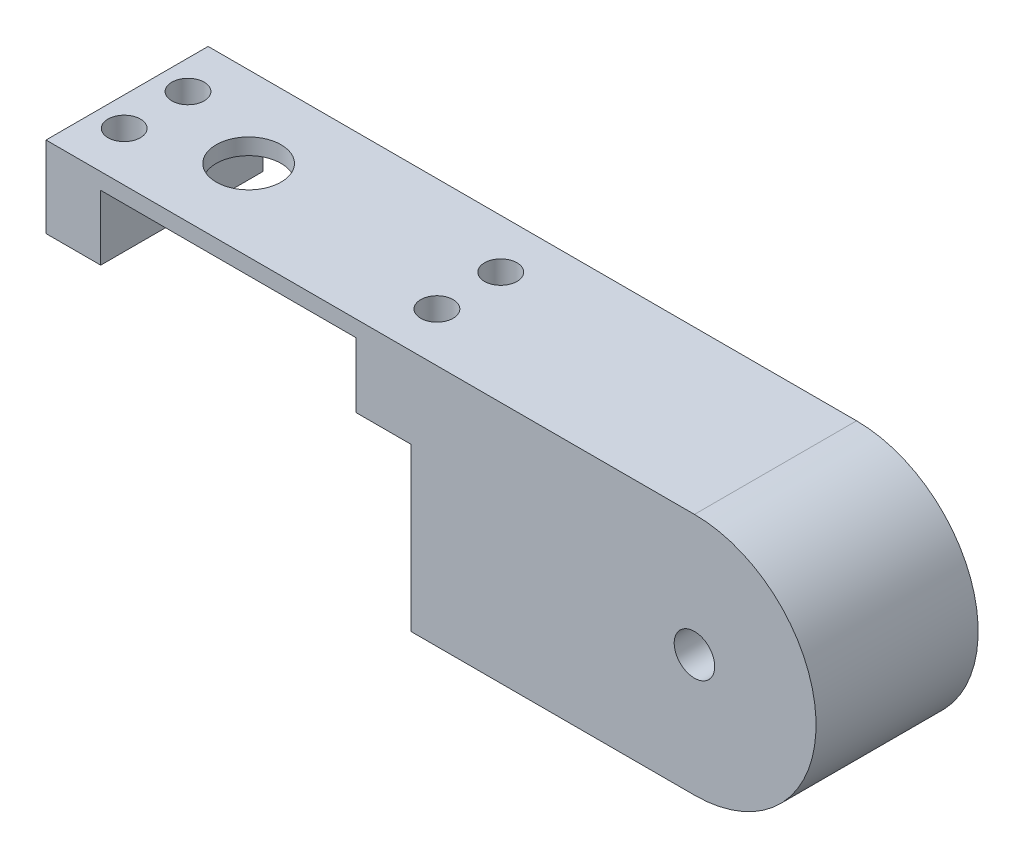
SolidWorks part; units mm, degrees
ref_plane "Front Plane" through (0, 0, 0) normal (0, 0, 1) x (1, 0, 0)
ref_plane "Top Plane" through (0, 0, 0) normal (0, 1, 0) x (1, 0, 0)
ref_plane "Right Plane" through (0, 0, 0) normal (1, 0, 0) x (0, 0, -1)
sketch "Sketch1" plane through (0, 0, 0) normal (0, 0, 1) x (1, 0, 0)
  line L1 (-50.8, -19.05) -> (50.8, -19.05)
  line L2 (-50.8, -19.05) -> (-50.8, 19.05)
  line L3 (-50.8, 19.05) -> (50.8, 19.05)
  line L4 (50.8, -19.05) -> (50.8, 19.05)
  line L5 (-50.8, -19.05) -> (50.8, 19.05) construction
  line L6 (-50.8, 19.05) -> (50.8, -19.05) construction
  circle A1 centre (50.8, 0) radius 19.05
  point P0 (0, 0)
  dimension "D1" = 38.1
  dimension "D2" = 101.6
extrude "Boss-Extrude1" add sketch "Sketch1" along normal blind 25.4 contours L2 L1 L4 L3 | A1
sketch "Sketch11" plane through (0, 0, 25.4) normal (0, 0, 1) x (1, 0, 0)
  circle A0 centre (50.8, 0) radius 3.175
  arc A1 (50.8, -19.05) -> (50.8, 19.05) centre (50.8, 0) ccw construction
  dimension "D1" = 6.35
extrude "Cut-Extrude6" cut sketch "Sketch11" against normal through all
sketch "Sketch12" plane through (0, 0, 25.4) normal (0, 0, 1) x (1, 0, 0)
  line L0 (-50.8, 19.05) -> (50.8, 19.05) construction
  line L1 (-50.8, -19.05) -> (6.35, -19.05)
  line L2 (-50.8, -19.05) -> (-50.8, 16.51)
  line L3 (-50.8, 16.51) -> (6.35, 16.51)
  line L4 (6.35, -19.05) -> (6.35, 16.51)
  dimension "D1" = 2.54
  dimension "D2" = 57.15
extrude "Cut-Extrude7" cut sketch "Sketch12" against normal through all
sketch "Sketch13" plane through (0, 19.05, 0) normal (0, 1, 0) x (1, 0, 0)
  line L5 (-50.8, -25.4) -> (-50.8, 0) construction
  line L6 (-50.8, -12.7) -> (50.8, -12.7) construction
  line L7 (50.8, -25.4) -> (50.8, 0) construction
  circle A1 centre (-31.75, -12.7) radius 5.08
  point P9 (-31.75, -12.7)
  dimension "D2" = 10.16
  dimension "D1" = 19.05
extrude "Cut-Extrude8" cut sketch "Sketch13" against normal through all
sketch "Sketch14" plane through (0, 16.51, 0) normal (0, -1, 0) x (1, 0, 0)
  line L0 (-50.8, 12.7) -> (6.35, 12.7) construction
  line L1 (-50.8, 25.4) -> (-42.225, 25.4)
  line L2 (-50.8, 25.4) -> (-50.8, 13.97)
  line L3 (-50.8, 13.97) -> (-42.225, 13.97)
  line L4 (-42.225, 25.4) -> (-42.225, 13.97)
  line L5 (-50.8, 0) -> (-50.8, 25.4) construction
  line L6 (6.35, 0) -> (6.35, 25.4) construction
  line L7 (-22.225, 25.4) -> (-22.225, 0) construction
  line L8 (6.35, 25.4) -> (-50.8, 25.4) construction
  line L9 (6.35, 0) -> (-50.8, 0) construction
  line L10 (6.35, 13.97) -> (-2.225, 13.97)
  line L11 (-2.225, 25.4) -> (-2.225, 13.97)
  line L12 (6.35, 25.4) -> (-2.225, 25.4)
  line L13 (6.35, 25.4) -> (6.35, 13.97)
  line L14 (6.35, 0) -> (6.35, 11.43)
  line L15 (6.35, 0) -> (-2.225, 0)
  line L16 (-2.225, 0) -> (-2.225, 11.43)
  line L17 (6.35, 11.43) -> (-2.225, 11.43)
  line L18 (-50.8, 11.43) -> (-42.225, 11.43)
  line L19 (-42.225, 0) -> (-42.225, 11.43)
  line L20 (-50.8, 0) -> (-42.225, 0)
  line L21 (-50.8, 0) -> (-50.8, 11.43)
  dimension "D1" = 39.9999
  dimension "D2" = 2.54
extrude "Boss-Extrude2" add sketch "Sketch14" along normal blind 10.16
ref_plane "Plane1" through (-50.8, 6.35, 25.4) normal (-1, 0, 0) x (0, 0, 1)
sketch "Sketch16" plane through (0, 6.35, 0) normal (0, -1, 0) x (1, 0, 0)
  line L0 (-50.8, 12.7) -> (6.35, 12.7) construction
  line L1 (-50.8, 11.43) -> (-50.8, 13.97) construction
  line L2 (6.35, 11.43) -> (6.35, 13.97) construction
  circle A0 centre (-46.2501, 17.7) radius 2.54
  circle A1 centre (2.7498, 17.7) radius 2.54
  circle A2 centre (-31.75, 12.7) radius 5.08 construction
  circle A3 centre (2.7498, 7.7) radius 2.54
  circle A4 centre (-46.2501, 7.7) radius 2.54
  point P10 (0, 0)
  point P13 (-46.2501, 19.685)
  point P14 (2.7498, 18.3849)
  dimension "D3" = 5.08
  dimension "D1" = 48.9999
  dimension "D2" = 14.5001
  dimension "D4" = 10
extrude "Cut-Extrude9" cut sketch "Sketch16" against normal through all
